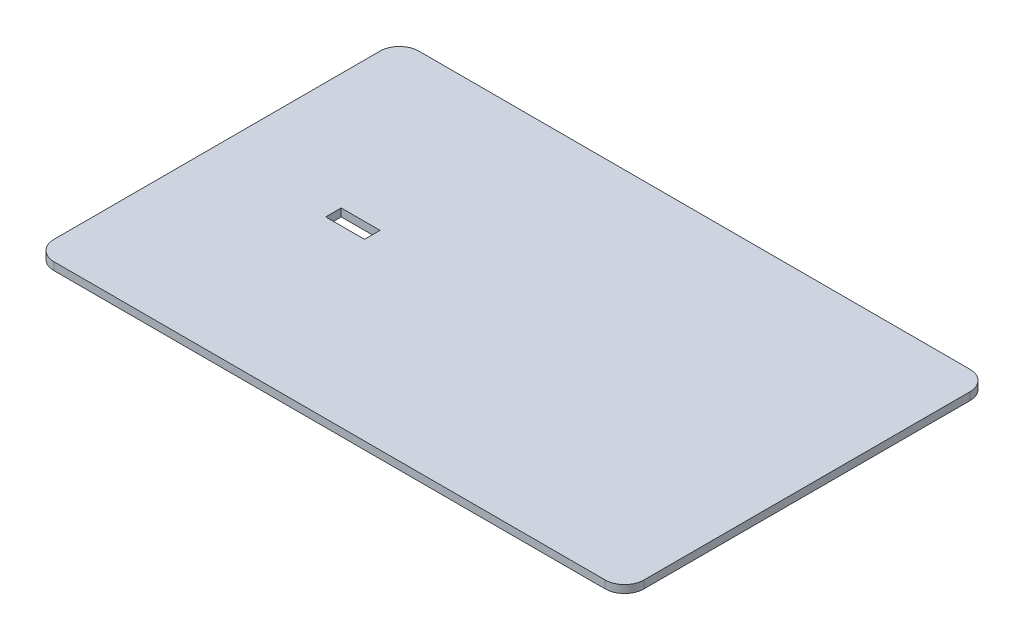
SolidWorks part; units mm, degrees
ref_plane "Front Plane" through (0, 0, 0) normal (0, 0, 1) x (1, 0, 0)
ref_plane "Top Plane" through (0, 0, 0) normal (0, 1, 0) x (1, 0, 0)
ref_plane "Right Plane" through (0, 0, 0) normal (1, 0, 0) x (0, 0, -1)
sketch "Sketch1" plane through (0, 0, 0) normal (0, 1, 0) x (1, 0, 0)
  line L1 (-38, 23.5) -> (38, 23.5)
  line L2 (-38, 23.5) -> (-38, -23.5)
  line L3 (-38, -23.5) -> (38, -23.5)
  line L4 (38, 23.5) -> (38, -23.5)
  line L5 (-38, 23.5) -> (38, -23.5) construction
  line L6 (-38, -23.5) -> (38, 23.5) construction
  point P0 (0, 0)
  dimension "D1" = 76
  dimension "D2" = 47
extrude "Boss-Extrude1" add sketch "Sketch1" against normal blind 1
sketch "Sketch2" plane through (0, -1, 0) normal (0, -1, 0) x (1, 0, 0)
  line L0 (-30.5, 18) -> (30.5, 18)
  line L1 (-33, 20.5) -> (33, 20.5)
  line L2 (-33, 20.5) -> (-33, -20.5)
  line L3 (-33, -20.5) -> (33, -20.5)
  line L4 (33, 20.5) -> (33, -20.5)
  line L5 (-33, 20.5) -> (33, -20.5) construction
  line L6 (-33, -20.5) -> (33, 20.5) construction
  line L7 (30.5, 18) -> (30.5, -18)
  line L8 (-30.5, -18) -> (30.5, -18)
  line L9 (-30.5, 18) -> (-30.5, -18)
  point P0 (0, 0)
  dimension "D1" = 66
  dimension "D2" = 41
  dimension "D3" = 2.5
extrude "Boss-Extrude2" add sketch "Sketch2" along normal blind 2.5
fillet "Fillet1" radius 2.5 4 edges at (38, -0.5, -23.5) (-38, -0.5, -23.5) (38, -0.5, 23.5) (-38, -0.5, 23.5)
sketch "Sketch4" plane through (0, 0, 0) normal (0, 1, 0) x (1, 0, 0)
  line L1 (-23, 1) -> (-18, 1)
  line L2 (-23, 1) -> (-23, -1)
  line L3 (-23, -1) -> (-18, -1)
  line L4 (-18, 1) -> (-18, -1)
  line L5 (-23, 1) -> (-18, -1) construction
  line L6 (-23, -1) -> (-18, 1) construction
  line L7 (-38, 21) -> (-38, -21) construction
  point P0 (-20.5, 0)
  point P5 (0, 0)
  dimension "D1" = 5
  dimension "D2" = 2
  dimension "D3" = 17.5
extrude "Cut-Extrude1" cut sketch "Sketch4" against normal up to surface (1 mm away) up to face at (0, -1, 0)
